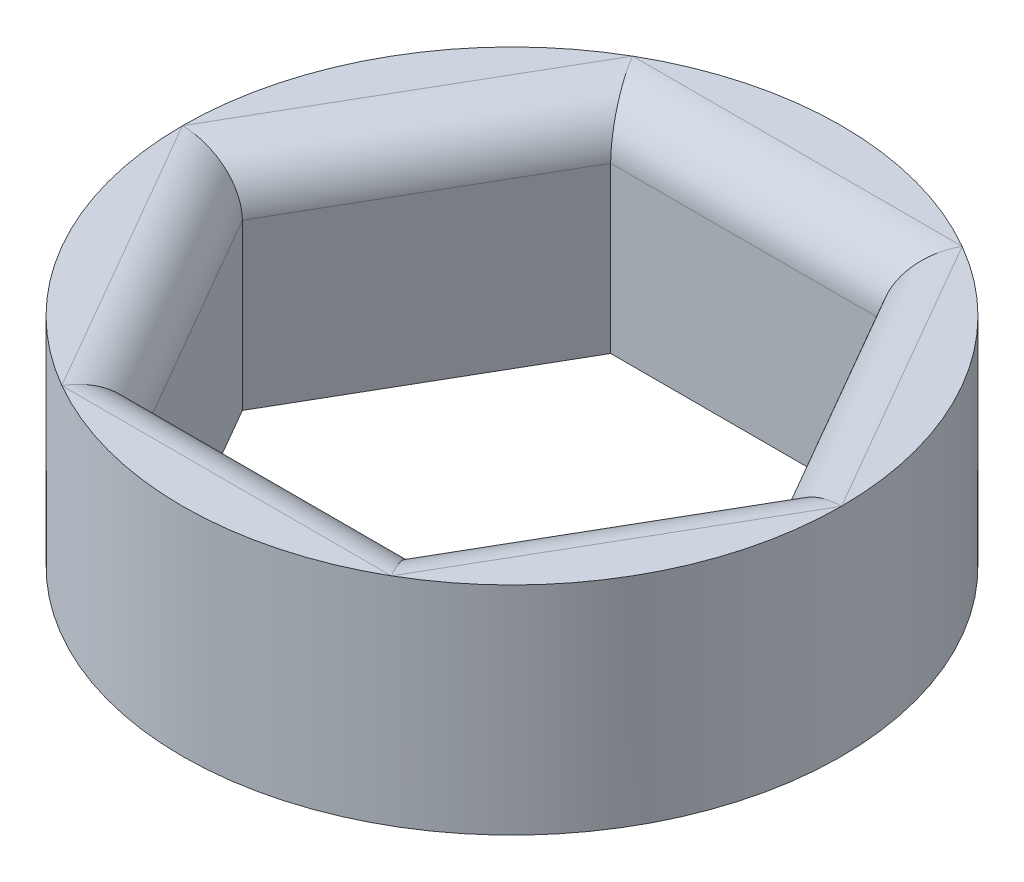
SolidWorks part; units mm, degrees
ref_plane "Front Plane" through (0, 0, 0) normal (0, 0, 1) x (1, 0, 0)
ref_plane "Top Plane" through (0, 0, 0) normal (0, 1, 0) x (1, 0, 0)
ref_plane "Right Plane" through (0, 0, 0) normal (1, 0, 0) x (0, 0, -1)
sketch "Sketch1" plane through (0, 0, 0) normal (0, 1, 0) x (1, 0, 0)
  line L1 (5.1962, 0) -> (2.5981, 4.5)
  line L2 (2.5981, 4.5) -> (-2.5981, 4.5)
  line L3 (-2.5981, 4.5) -> (-5.1962, 0)
  line L4 (-5.1962, 0) -> (-2.5981, -4.5)
  line L5 (-2.5981, -4.5) -> (2.5981, -4.5)
  line L6 (2.5981, -4.5) -> (5.1962, 0)
  circle A0 centre (0, 0) radius 6.35
  circle A1 centre (0, 0) radius 4.5 construction
  dimension "D1" = 12.7
  dimension "D3" = 9
extrude "Boss-Extrude1" add sketch "Sketch1" along normal blind 4.175
fillet "Fillet1" radius 1 6 edges at (0, 4.175, -4.5) (-3.8971, 4.175, 2.25) (0, 4.175, 4.5) (3.8971, 4.175, 2.25) (3.8971, 4.175, -2.25) (-3.8971, 4.175, -2.25)
